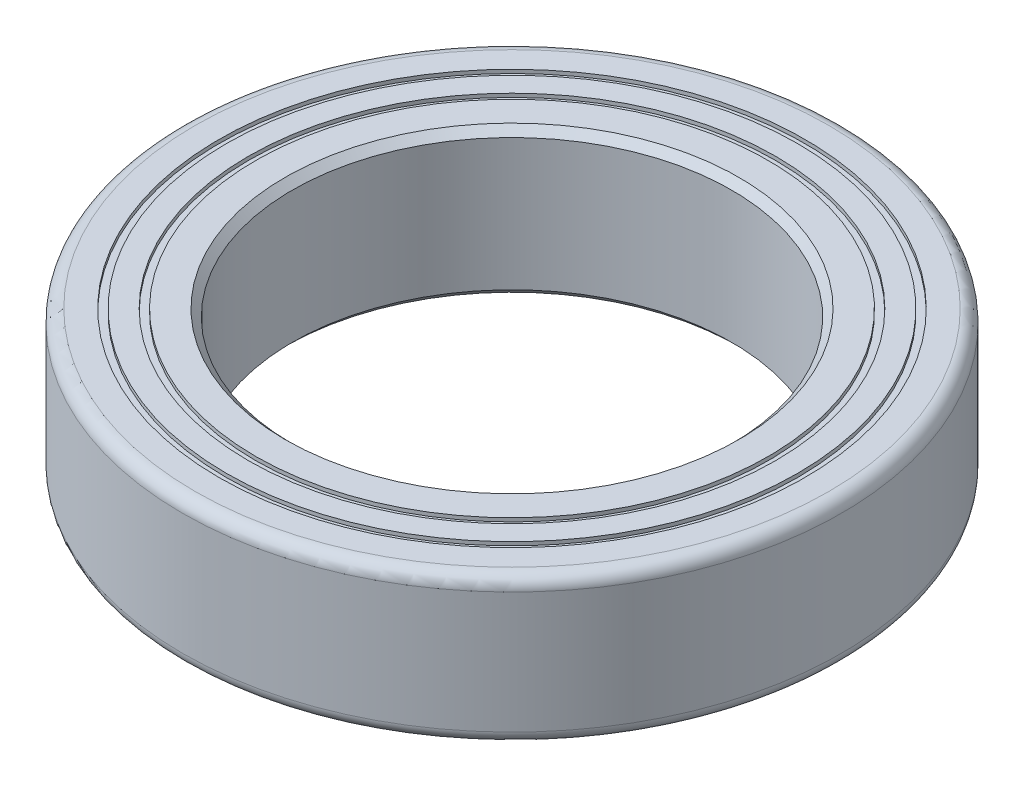
SolidWorks part; units mm, degrees
ref_plane "Front Plane" through (0, 0, 0) normal (0, 0, 1) x (1, 0, 0)
ref_plane "Top Plane" through (0, 0, 0) normal (0, 1, 0) x (1, 0, 0)
ref_plane "Right Plane" through (0, 0, 0) normal (1, 0, 0) x (0, 0, -1)
sketch "Sketch1" plane through (0, 0, 0) normal (0, 0, 1) x (1, 0, 0)
  line L0 (0, 0) -> (6, 0) construction
  line L1 (9, 0) -> (9, 4)
  line L3 (0, 2) -> (0, 0) construction
  line L4 (6, 0) -> (6, 4)
  line L5 (6, 0) -> (7, 0)
  line L6 (7, 0) -> (7, 0.1)
  line L7 (7, 0.1) -> (7.2, 0.1)
  line L8 (7.2, 0.1) -> (7.2, 0)
  line L9 (7.2, 0) -> (7.8, 0)
  line L10 (7.5, 0) -> (7.5, 2) construction
  line L11 (9, 2) -> (6, 2) construction
  line L12 (6, 2) -> (0, 2) construction
  line L13 (7.8, 0.1) -> (7.8, 0)
  line L14 (8, 0.1) -> (7.8, 0.1)
  line L15 (8, 0) -> (8, 0.1)
  line L16 (9, 0) -> (8, 0)
  line L17 (9, 4) -> (8, 4)
  line L18 (8, 4) -> (8, 3.9)
  line L19 (8, 3.9) -> (7.8, 3.9)
  line L20 (7.8, 3.9) -> (7.8, 4)
  line L21 (7.2, 4) -> (7.8, 4)
  line L22 (7.2, 3.9) -> (7.2, 4)
  line L23 (7, 3.9) -> (7.2, 3.9)
  line L24 (7, 4) -> (7, 3.9)
  line L25 (6, 4) -> (7, 4)
  dimension "D1" = 9
  dimension "D2" = 6
  dimension "D4" = 1
  dimension "D5" = 0.2
  dimension "D6" = 0.1
  dimension "D3" = 4
revolve "Revolve1" add sketch "Sketch1" angle 360 about L3
fillet "Fillet2" radius 0.344 2 edges at (0, 0, 9) (0, 4, 9)
chamfer "Chamfer2" distance 0.2 angle 45 2 edges at (0, 0, 6) (0, 4, 6)
equation "\"Ratio\"= 15"
equation "\"Hull Diameter\"= 3.5in"
equation "\"Fixed Ring Diameter\"= 76"
equation "\"Fixed Pin Diameter\"= 6"
equation "\"Output Ring Diameter\"= 40"
equation "\"Output Pin Diameter\"= 6"
equation "\"Disk Bearing Inner Diameter\"= 9"
equation "\"Disk Bearing Outer Diameter\"= 17"
equation "\"Disk Bearing Height\"= 5"
equation "\"Shaft Bearing Inner Diameter\"= 15"
equation "\"Shaft Bearing Outer Diameter\"= 21"
equation "\"Shaft Bearing Height\"= 4"
equation "\"Eccentricity\"= 1.5"
equation "\"Disk Height\"= 8"
equation "\"Disk Spacing\"= 5"
equation "\"Hull Height\"= 40"
equation "\"Shaft End Bearing Inner Diameter\"= 12"
equation "\"Shaft End Bearing Outer Diameter\"= 18"
equation "\"Shaft End Bearing Height\"= 4"
equation "\"Output Bearing Inner Diameter\"= 55"
equation "\"Output Bearing Outer Diameter\"= 72"
equation "\"Outer Bearing Height\"= 9"
equation "\"D3@Sketch1\"=\"Shaft End Bearing Height\""
equation "\"D2@Sketch1\"=\"Shaft End Bearing Inner Diameter\"/2"
equation "\"D1@Sketch1\"=\"Shaft End Bearing Outer Diameter\"/2"
